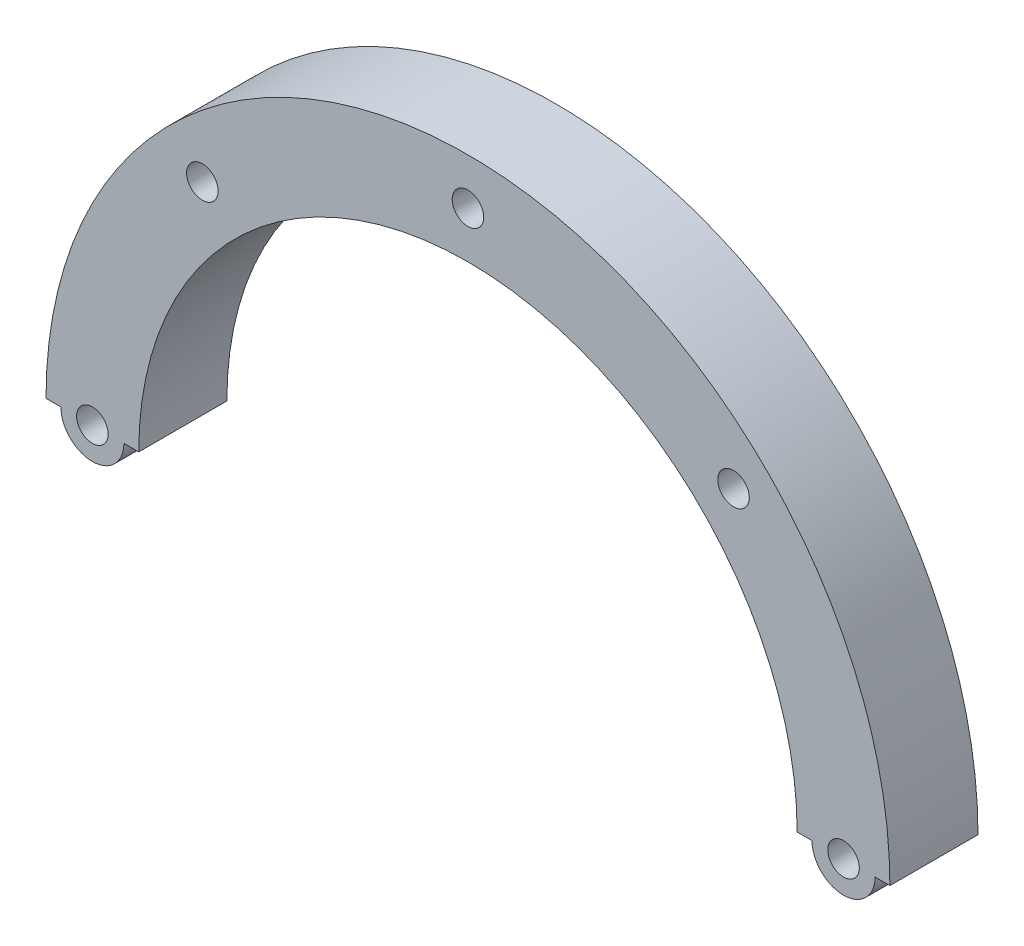
SolidWorks part; units mm, degrees
ref_plane "Alzado" through (0, 0, 0) normal (0, 0, 1) x (1, 0, 0)
ref_plane "Planta" through (0, 0, 0) normal (0, 1, 0) x (1, 0, 0)
ref_plane "Vista lateral" through (0, 0, 0) normal (1, 0, 0) x (0, 0, -1)
sketch "Croquis1" plane through (0, 0, 0) normal (0, 0, 1) x (1, 0, 0)
  line L0 (-45.5, 0) -> (-35.5, 0)
  line L1 (35.5, 0) -> (45.5, 0)
  arc A0 (35.5, 0) -> (-35.5, 0) centre (0, 0) ccw
  arc A1 (45.5, 0) -> (-45.5, 0) centre (0, 0) ccw
  circle A3 centre (0, 0) radius 45.5 construction
  circle A4 centre (0, 0) radius 35.5 construction
  point P6 (33.9488, 10.3792)
  point P7 (45.5, 0)
  dimension "D1" = 71
  dimension "D2" = 10
extrude "Saliente-Extruir1" add sketch "Croquis1" along normal blind 9.5
sketch "Croquis2" plane through (0, 0, 9.5) normal (0, 0, 1) x (1, 0, 0)
  line L1 (0, 35.5) -> (0, 45.5) construction
  circle A1 centre (0, 40.5) radius 1.7
  arc A2 (35.5, 0) -> (-35.5, 0) centre (0, 0) ccw construction
  arc A3 (45.5, 0) -> (-45.5, 0) centre (0, 0) ccw construction
  circle A4 centre (28.6378, 28.6378) radius 1.7
  circle A5 centre (40.5, 0) radius 1.7
  circle A6 centre (-40.5, 0) radius 1.7
  circle A7 centre (-28.6378, 28.6378) radius 1.7
  point P17 (0, 0)
  dimension "D1" = 3.4
  dimension "D2" = 3
extrude "Cortar-Extruir1" cut sketch "Croquis2" against normal through all
sketch "Croquis3" plane through (0, 0, 9.5) normal (0, 0, 1) x (1, 0, 0)
  line L0 (0, 0) -> (0, 9.7842) construction
  circle A0 centre (-40.5, 0) radius 3.4
  circle A1 centre (-40.5, 0) radius 1.7
  circle A2 centre (40.5, 0) radius 1.7
  circle A3 centre (40.5, 0) radius 3.4
  dimension "D1" = 6.8
extrude "Saliente-Extruir2" add sketch "Croquis3" against normal up to surface (9.5 mm away) up to face at (1.7, 40.5, 0)
